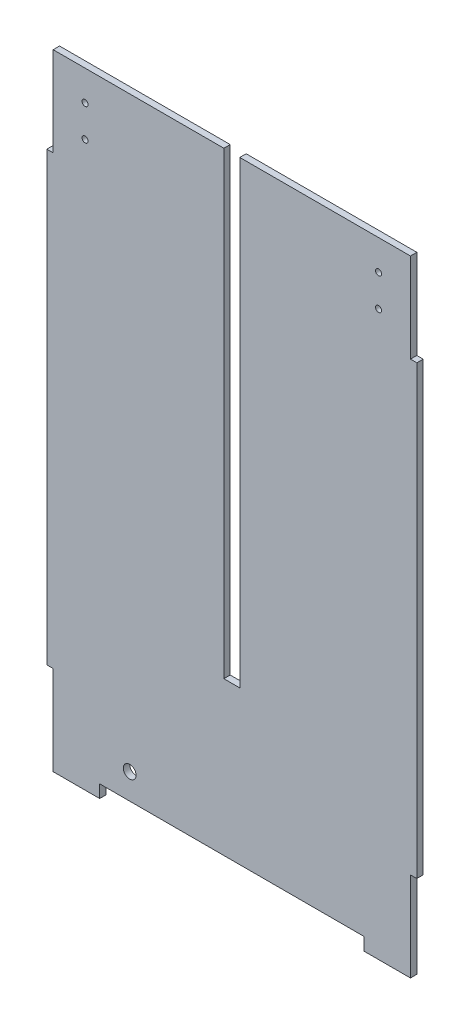
SolidWorks part; units mm, degrees
ref_plane "Front Plane" through (0, 0, 0) normal (0, 0, 1) x (1, 0, 0)
ref_plane "Top Plane" through (0, 0, 0) normal (0, 1, 0) x (1, 0, 0)
ref_plane "Right Plane" through (0, 0, 0) normal (1, 0, 0) x (0, 0, -1)
sketch "Sketch2" plane through (0, 0, 0) normal (0, 0, 1) x (1, 0, 0)
  line L0 (0, 152.4) -> (0, -152.4) construction
  line L1 (-88.9, 152.4) -> (88.9, 152.4)
  line L2 (-88.9, 152.4) -> (-88.9, -152.4)
  line L3 (-88.9, -152.4) -> (88.9, -152.4)
  line L4 (88.9, 152.4) -> (88.9, -152.4)
  line L5 (-88.9, 107.95) -> (-88.9, 63.5)
  line L6 (-88.9, 152.4) -> (-92.075, 152.4)
  line L7 (-88.9, 152.4) -> (-88.9, 107.95)
  line L8 (-88.9, 107.95) -> (-92.075, 107.95)
  line L9 (-92.075, 152.4) -> (-92.075, 107.95)
  line L10 (88.9, 152.4) -> (92.075, 152.4)
  line L11 (88.9, 152.4) -> (88.9, 107.95)
  line L12 (88.9, 107.95) -> (92.075, 107.95)
  line L13 (92.075, 152.4) -> (92.075, 107.95)
  line L14 (-65.7679, -152.4) -> (-92.075, -152.4)
  line L15 (-65.7679, -152.4) -> (-65.7679, -158.75)
  line L16 (-65.7679, -158.75) -> (-92.075, -158.75)
  line L17 (-92.075, -152.4) -> (-92.075, -158.75)
  line L18 (-88.9, 107.95) -> (-92.075, 107.95)
  line L19 (-92.075, 107.95) -> (-92.075, 63.5)
  line L20 (-88.9, 63.5) -> (-92.075, 63.5)
  line L21 (88.9, 107.95) -> (88.9, 63.5)
  line L22 (88.9, 107.95) -> (92.075, 107.95)
  line L23 (92.075, 107.95) -> (92.075, 63.5)
  line L24 (88.9, 63.5) -> (92.075, 63.5)
  line L25 (-88.9, 63.5) -> (-88.9, 19.05)
  line L26 (-88.9, 63.5) -> (-92.075, 63.5)
  line L27 (-92.075, 63.5) -> (-92.075, 19.05)
  line L28 (-88.9, 19.05) -> (-92.075, 19.05)
  line L29 (88.9, 63.5) -> (88.9, 19.05)
  line L30 (88.9, 63.5) -> (92.075, 63.5)
  line L31 (92.075, 63.5) -> (92.075, 19.05)
  line L32 (88.9, 19.05) -> (92.075, 19.05)
  line L33 (-88.9, 19.05) -> (-88.9, -25.4)
  line L34 (-88.9, 19.05) -> (-92.075, 19.05)
  line L35 (-92.075, 19.05) -> (-92.075, -25.4)
  line L36 (-88.9, -25.4) -> (-92.075, -25.4)
  line L37 (88.9, 19.05) -> (88.9, -25.4)
  line L38 (88.9, 19.05) -> (92.075, 19.05)
  line L39 (92.075, 19.05) -> (92.075, -25.4)
  line L40 (88.9, -25.4) -> (92.075, -25.4)
  line L41 (-88.9, -25.4) -> (-88.9, -69.85)
  line L42 (-88.9, -25.4) -> (-92.075, -25.4)
  line L43 (-92.075, -25.4) -> (-92.075, -69.85)
  line L44 (-88.9, -69.85) -> (-92.075, -69.85)
  line L45 (88.9, -25.4) -> (88.9, -69.85)
  line L46 (88.9, -25.4) -> (92.075, -25.4)
  line L47 (92.075, -25.4) -> (92.075, -69.85)
  line L48 (88.9, -69.85) -> (92.075, -69.85)
  line L49 (-88.9, -69.85) -> (-88.9, -114.3)
  line L50 (-88.9, -69.85) -> (-92.075, -69.85)
  line L51 (-92.075, -69.85) -> (-92.075, -114.3)
  line L52 (-88.9, -114.3) -> (-92.075, -114.3)
  line L53 (88.9, -69.85) -> (88.9, -114.3)
  line L54 (88.9, -69.85) -> (92.075, -69.85)
  line L55 (92.075, -69.85) -> (92.075, -114.3)
  line L56 (88.9, -114.3) -> (92.075, -114.3)
  line L57 (-88.9, -114.3) -> (-88.9, -158.75)
  line L58 (-88.9, -114.3) -> (-92.075, -114.3)
  line L59 (-92.075, -114.3) -> (-92.075, -158.75)
  line L60 (-88.9, -158.75) -> (-92.075, -158.75)
  line L61 (88.9, -114.3) -> (88.9, -158.75)
  line L62 (88.9, -114.3) -> (92.075, -114.3)
  line L63 (92.075, -114.3) -> (92.075, -158.75)
  line L64 (88.9, -158.75) -> (92.075, -158.75)
  line L65 (-39.4607, -152.4) -> (-39.4607, -158.75)
  line L66 (-39.4607, -152.4) -> (-65.7679, -152.4)
  line L67 (-65.7679, -152.4) -> (-65.7679, -158.75)
  line L68 (-39.4607, -158.75) -> (-65.7679, -158.75)
  line L69 (-13.1536, -152.4) -> (-13.1536, -158.75)
  line L70 (-13.1536, -152.4) -> (-39.4607, -152.4)
  line L71 (-39.4607, -152.4) -> (-39.4607, -158.75)
  line L72 (-13.1536, -158.75) -> (-39.4607, -158.75)
  line L73 (13.1536, -152.4) -> (13.1536, -158.75)
  line L74 (13.1536, -152.4) -> (-13.1536, -152.4)
  line L75 (-13.1536, -152.4) -> (-13.1536, -158.75)
  line L76 (13.1536, -158.75) -> (-13.1536, -158.75)
  line L77 (39.4607, -152.4) -> (39.4607, -158.75)
  line L78 (39.4607, -152.4) -> (13.1536, -152.4)
  line L79 (13.1536, -152.4) -> (13.1536, -158.75)
  line L80 (39.4607, -158.75) -> (13.1536, -158.75)
  line L81 (65.7679, -152.4) -> (65.7679, -158.75)
  line L82 (65.7679, -152.4) -> (39.4607, -152.4)
  line L83 (39.4607, -152.4) -> (39.4607, -158.75)
  line L84 (65.7679, -158.75) -> (39.4607, -158.75)
  line L85 (92.075, -152.4) -> (92.075, -158.75)
  line L86 (92.075, -152.4) -> (65.7679, -152.4)
  line L87 (65.7679, -152.4) -> (65.7679, -158.75)
  line L88 (92.075, -158.75) -> (65.7679, -158.75)
  point P6 (0, 0)
  dimension "D1" = 177.8
  dimension "D2" = 184.15
  dimension "D3" = 304.8
  dimension "D4" = 311.15
  dimension "D6" = 44.45
  dimension "D8" = 26.3071
  dimension "D5" = 7
  dimension "D7" = 7
extrude "Boss-Extrude1" add sketch "Sketch2" along normal blind 3.175 contours L0 L1 L2 L3 | L1 L0 L3 L4 | L20 L2 L8 L19 | L36 L2 L28 L35 | L52 L2 L44 L51 | L3 L57 L16 L15 | L72 L69 L3 L65 | L80 L77 L3 L73 | L4 L56 L55 L48 | L4 L40 L39 L32 | L4 L24 L23 L12 | L88 L61 L3 L81 region at (44.45, 0, 0) region at (-44.45, 0, 0) region at (-26.3071, -155.575, 0) region at (26.3071, -155.575, 0) region at (-90.4875, 85.725, 0) region at (90.4875, 85.725, 0) region at (-77.3339, -155.575, 0) region at (77.3339, -155.575, 0) region at (-90.4875, -3.175, 0) region at (90.4875, -3.175, 0) region at (-90.4875, -92.075, 0) region at (90.4875, -92.075, 0)
sketch "Sketch3" plane through (0, 0, 3.175) normal (0, 0, 1) x (1, 0, 0)
  line L0 (-88.9, 152.4) -> (88.9, 152.4) construction
  line L1 (-3.9688, 152.4) -> (3.9687, 152.4)
  line L2 (-3.9688, 152.4) -> (-3.9687, -76.2)
  line L3 (-3.9687, -76.2) -> (3.9688, -76.2)
  line L4 (3.9687, 152.4) -> (3.9688, -76.2)
  line L5 (0, -76.2) -> (0, 0) construction
  dimension "D1" = 7.9375
  dimension "D2" = 228.6
extrude "Cut-Extrude1" cut sketch "Sketch3" against normal through all
sketch "Sketch4" plane through (0, 0, 3.175) normal (0, 0, 1) x (1, 0, 0)
  line L0 (-65.7679, -152.4) -> (-39.4607, -152.4) construction
  line L1 (-88.9, -114.3) -> (-88.9, -158.75) construction
  circle A0 centre (-50.8, -139.7) radius 3.175
  dimension "D1" = 6.35
  dimension "D2" = 12.7
  dimension "D3" = 38.1
extrude "Cut-Extrude2" cut sketch "Sketch4" against normal through all
sketch "Sketch5" plane through (0, 0, 3.175) normal (0, 0, 1) x (1, 0, 0)
  line L0 (0, -152.4) -> (0, 152.4) construction
  line L1 (-13.1536, -152.4) -> (13.1536, -152.4) construction
  line L2 (3.9687, 152.4) -> (88.9, 152.4) construction
  line L3 (-88.9, 152.4) -> (-3.9688, 152.4) construction
  line L5 (-92.075, 107.95) -> (-92.075, 63.5) construction
  circle A0 centre (-73.025, 137.4) radius 1.5
  circle A1 centre (-73.025, 121.65) radius 1.5
  circle A2 centre (73.025, 121.65) radius 1.5
  circle A3 centre (73.025, 137.4) radius 1.5
  dimension "D1" = 15.75
  dimension "D2" = 15
  dimension "D4" = 3
  dimension "D5" = 3
  dimension "D3" = 19.05
extrude "Cut-Extrude3" cut sketch "Sketch5" against normal up to surface (3.175 mm away) up to face at (-47.625, -139.7, 0)
sketch "Sketch6" plane through (0, 0, 3.175) normal (0, 0, 1) x (1, 0, 0)
  line L1 (-92.075, 63.5) -> (-88.9, 63.5)
  line L2 (-92.075, 63.5) -> (-92.075, 19.05)
  line L3 (-92.075, 19.05) -> (-88.9, 19.05)
  line L4 (-88.9, 63.5) -> (-88.9, 19.05)
  line L5 (-92.075, -25.4) -> (-88.9, -25.4)
  line L6 (-92.075, -25.4) -> (-92.075, -69.85)
  line L7 (-92.075, -69.85) -> (-88.9, -69.85)
  line L8 (-88.9, -25.4) -> (-88.9, -69.85)
  line L9 (92.075, 63.5) -> (88.9, 63.5)
  line L10 (92.075, 63.5) -> (92.075, 19.05)
  line L11 (92.075, 19.05) -> (88.9, 19.05)
  line L12 (88.9, 63.5) -> (88.9, 19.05)
  line L13 (88.9, -25.4) -> (92.075, -25.4)
  line L14 (88.9, -25.4) -> (88.9, -69.85)
  line L15 (88.9, -69.85) -> (92.075, -69.85)
  line L16 (92.075, -25.4) -> (92.075, -69.85)
extrude "Boss-Extrude2" add sketch "Sketch6" against normal up to surface (3.175 mm away) up to face at (74.525, 137.4, 0)
sketch "Sketch7" plane through (0, 0, 3.175) normal (0, 0, 1) x (1, 0, 0)
  line L1 (-39.4607, -152.4) -> (-13.1536, -152.4)
  line L2 (-39.4607, -152.4) -> (-39.4607, -158.75)
  line L3 (-39.4607, -158.75) -> (-13.1536, -158.75)
  line L4 (-13.1536, -152.4) -> (-13.1536, -158.75)
  line L5 (13.1536, -152.4) -> (39.4607, -152.4)
  line L6 (13.1536, -152.4) -> (13.1536, -158.75)
  line L7 (13.1536, -158.75) -> (39.4607, -158.75)
  line L8 (39.4607, -152.4) -> (39.4607, -158.75)
extrude "Cut-Extrude4" cut sketch "Sketch7" against normal up to surface (3.175 mm away) up to face at (0, -62.5929, 0)
equation "\"Height\"= 12in"
equation "\"Depth\"= 7in"
equation "\"WallThickness\"= 0.125in"
equation "\"FloorThickness\"= 0.25in"
equation "\"D1@Sketch2\"=\"Depth\""
equation "\"D2@Sketch2\"=\"D1@Sketch2\"+2*\"WallThickness\""
equation "\"D3@Sketch2\"=\"Height\""
equation "\"D4@Sketch2\"=\"D3@Sketch2\"+\"FloorThickness\""
equation "\"D6@Sketch2\"=\"D4@Sketch2\"/\"D5@Sketch2\""
equation "\"D8@Sketch2\"=\"D2@Sketch2\"/\"D7@Sketch2\""
equation "\"D1@Boss-Extrude1\"=\"WallThickness\""
equation "\"Width\" = 30in"
